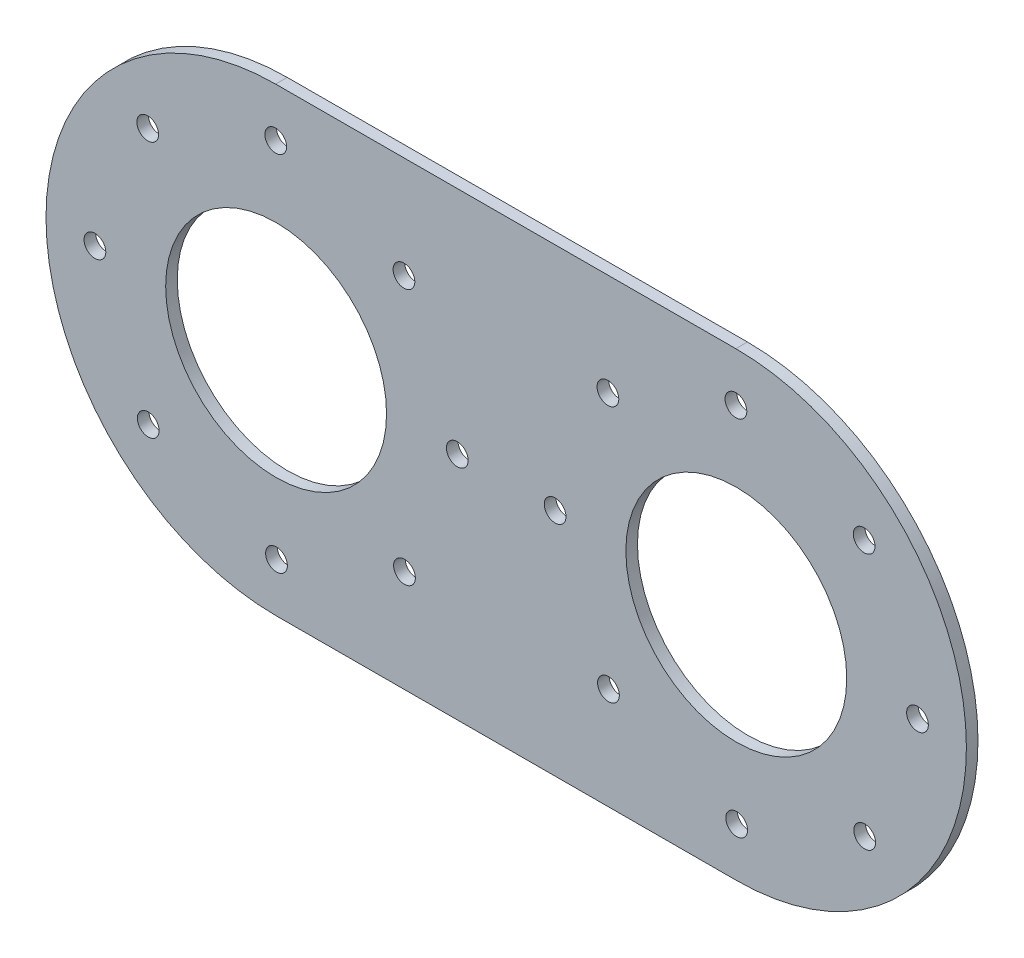
SolidWorks part; units mm, degrees
ref_plane "Front Plane" through (0, 0, 0) normal (0, 0, 1) x (1, 0, 0)
ref_plane "Top Plane" through (0, 0, 0) normal (0, 1, 0) x (1, 0, 0)
ref_plane "Right Plane" through (0, 0, 0) normal (1, 0, 0) x (0, 0, -1)
sketch "Sketch1" plane through (0, 0, 0) normal (0, 0, 1) x (1, 0, 0)
  line L0 (47.625, -3.3973) -> (-15.875, -3.5277)
  line L1 (-0.0326, 12.3799) -> (31.7174, 12.4451)
  line L2 (0.0326, -19.37) -> (31.7826, -19.3048)
  circle A0 centre (40.607, -12.2506) radius 0.75
  circle A1 centre (31.7757, -15.9299) radius 0.75
  circle A2 centre (0, -3.4951) radius 15.875
  circle A3 centre (31.75, -3.4299) radius 15.875
  circle A4 centre (22.9293, -12.2869) radius 0.75
  circle A6 centre (-12.5, -3.5207) radius 0.75
  circle A7 centre (-8.857, 5.3256) radius 0.75
  circle A8 centre (-0.0257, 9.0049) radius 0.75
  circle A9 centre (8.8207, 5.3619) radius 0.75
  circle A10 centre (12.5, -3.4694) radius 0.75
  circle A11 centre (8.857, -12.3158) radius 0.75
  circle A12 centre (0.0257, -15.9951) radius 0.75
  circle A13 centre (-8.8207, -12.3521) radius 0.75
  circle A14 centre (44.25, -3.4042) radius 0.75
  circle A15 centre (19.25, -3.4555) radius 0.75
  circle A23 centre (0, -3.4951) radius 7.62
  circle A24 centre (31.75, -3.4299) radius 7.62
  circle A25 centre (22.893, 5.3908) radius 0.75
  circle A26 centre (31.7243, 9.0701) radius 0.75
  circle A27 centre (40.5707, 5.4271) radius 0.75
  point P7 (31.75, -3.4299)
  point P8 (0, -3.4951)
  point P28 (0, -3.4951)
  point P46 (31.75, -3.4299)
  dimension "D2" = 12.5
  dimension "D4" = 12.5
  dimension "D5" = 1.5
  dimension "D6" = 1.5
  dimension "D8" = 15.24
  dimension "D9" = 15.24
  dimension "D10" = 31.75
  dimension "D1" = 31.75
  dimension "D11" = 31.75
  dimension "D3" = 8
  dimension "D7" = 8
extrude "Boss-Extrude1" add sketch "Sketch1" along normal blind 0.8 contours A15 L0 A3 A14 A4 A1 | A15 L0 A14 A3 A27 A26 A25 | A10 L0 A2 A6 A9 A8 A7 | A10 L0 A6 A2 A13 A12 A11 | A3 L1 A2 | A3 A2 L2 region at (31.766, -11.2201, 0) region at (31.734, 4.3604, 0) region at (15.8497, 8.8665, 0) region at (15.9003, -15.7914, 0) region at (-0.016, 4.2952, 0) region at (0.016, -11.2854, 0)
